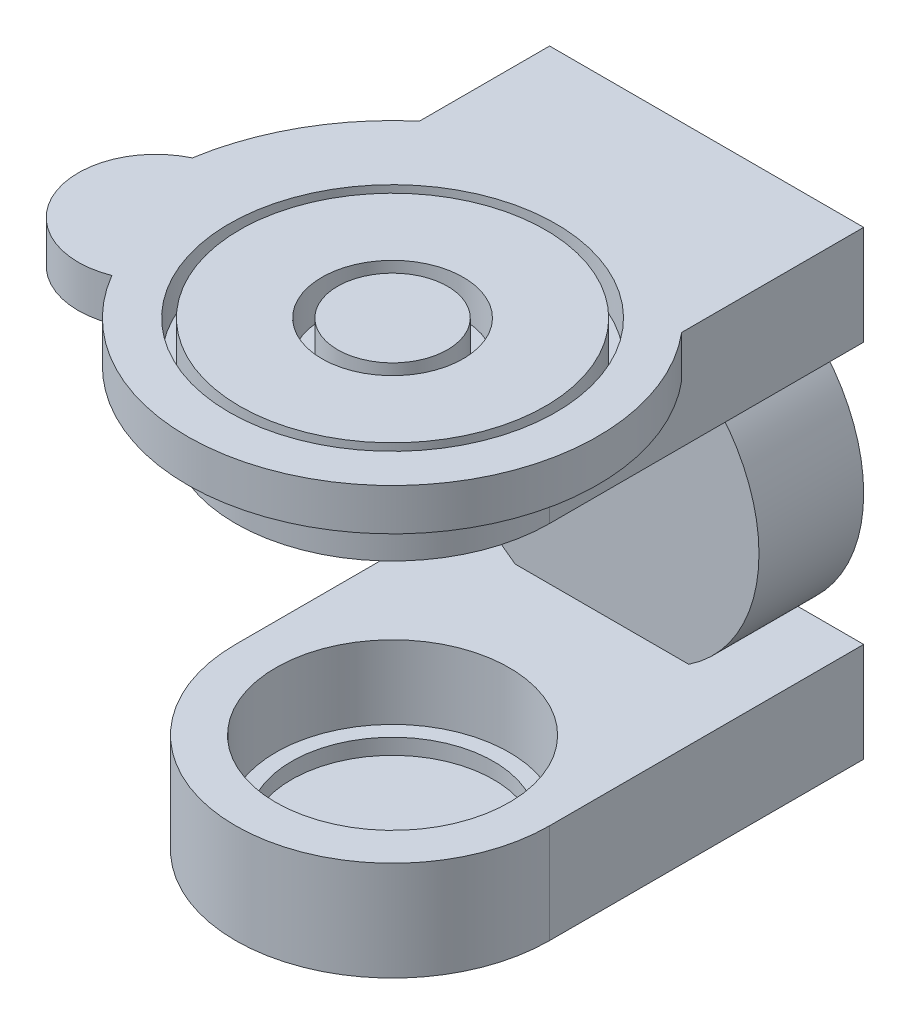
SolidWorks part; units mm, degrees
ref_plane "Спереди" through (0, 0, 0) normal (0, 0, 1) x (1, 0, 0)
ref_plane "Сверху" through (0, 0, 0) normal (0, 1, 0) x (1, 0, 0)
ref_plane "Справа" through (0, 0, 0) normal (1, 0, 0) x (0, 0, -1)
sketch "Эскиз основы" plane through (0, 0, 0) normal (0, 0, 1) x (1, 0, 0)
  circle A0 centre (0, 0) radius 15
  dimension "D1" = 30
extrude "Под крепеж" add sketch "Эскиз основы" along normal blind 10
ref_plane "Плоскость1" through (0, -15, 0) normal (0, -1, 0) x (-1, 0, 0)
sketch "Эскиз2" plane through (0, -15, 0) normal (0, -1, 0) x (-1, 0, 0)
  line L0 (-15, -10) -> (-15, -30)
  line L1 (15, 0) -> (-15, 0)
  line L2 (15, 0) -> (15, -10)
  line L3 (15, -10) -> (-15, -10)
  line L4 (-15, 0) -> (-15, -10)
  line L6 (15, -30) -> (15, -10)
  arc A0 (15, -30) -> (-15, -30) centre (0, -30) cw
  point P6 (0, -45)
  point P9 (0, -10)
  dimension "D1" = 15
  dimension "D2" = 20
extrude "Для крепления клешней" add sketch "Эскиз2" against normal blind 2.5 and the other way blind 7 contours L1 L4 L3 L2 | L6 L3 L0 region at (0, -15, 26.0668) region at (0, -15, 5)
sketch "Эскиз под подшипник" plane through (0, -12.5, 0) normal (0, 1, 0) x (1, 0, 0)
  line L0 (0, 0) -> (0, -30) construction
  line L1 (0, -30) -> (15, -30) construction
  circle A0 centre (0, -30) radius 11.15
  circle A1 centre (0, -30) radius 9.65
  dimension "D1" = 22.3
  dimension "D2" = 19.3
extrude "Выемка под подшипник" cut sketch "Эскиз под подшипник" against normal blind 8.5 contours A1 | A1 region at (0, -12.5, 30)
extrude "Вырез под подшипник" cut sketch "Эскиз4<3>" against normal blind 7 contours A0 A1 region at (-10.8346, -12.5, 30)
sketch "Эскиз4<3>" plane through (0, -12.5, 0) normal (0, 1, 0) x (1, 0, 0) same geometry as "Эскиз под подшипник"
mirror "Зеркальное отражение2" about plane through (0, 0, 0) normal (0, 1, 0) of "Вырез под подшипник", "Выемка под подшипник", "Для крепления клешней"
sketch "Эскиз под резистор" plane through (0, 22, 0) normal (0, 1, 0) x (1, 0, 0)
  line L0 (-15, -30) -> (15, -30) construction
  circle A0 centre (0, -30) radius 3.6
  dimension "D1" = 7.2
extrude "Вырез(отверстие) под резистор" cut sketch "Эскиз под резистор" against normal up to next
sketch "Эскиз4" plane through (0, 22, 0) normal (0, 1, 0) x (1, 0, 0)
  line L0 (0, -8.9) -> (0, -47.6) construction
  line L1 (15.6, -30) -> (-15.6, -30) construction
  line L2 (14.9, -17.2662) -> (14.9, -11.5209)
  line L6 (-15, 0) -> (-15, -30)
  line L7 (15, -30) -> (15, 0)
  line L8 (-15, 0) -> (15, 0)
  line L12 (0, -30) -> (-20.8576, -33.1889) construction
  line L13 (-18.6886, -30.8341) -> (-21.1599, -31.2119)
  line L14 (-16.4093, -32.5088) -> (-22.8347, -33.4912)
  line L15 (-18.0841, -34.7881) -> (-20.5554, -35.1659)
  line L16 (12.9, -18.0271) -> (12.9, -11.5209)
  circle A4 centre (0, -30) radius 14.6
  circle A5 centre (0, -30) radius 6.75
  circle A8 centre (0, -30) radius 5.25
  circle A11 centre (0, -30) radius 15
  arc A13 (-16.9219, -39.8898) -> (-22.8049, -26.3195) centre (-19.622, -33) cw
  arc A16 (-22.8049, -26.3195) -> (1.9933, -6.9862) centre (0, -30) cw
  arc A17 (1.9933, -6.9862) -> (14.9, -11.5209) centre (7.65, -11.5209) cw
  circle A18 centre (0, -30) radius 15.6
  arc A19 (12.9, -18.0271) -> (-16.1053, -37.0979) centre (0, -30) cw
  arc A20 (-20.5554, -35.1659) -> (-21.1599, -31.2119) centre (-20.8576, -33.1889) cw
  arc A21 (-18.6886, -30.8341) -> (-18.0841, -34.7881) centre (-18.3863, -32.8111) cw
  arc A22 (-16.1053, -37.0979) -> (-20.9823, -27.7741) centre (-19.622, -33) cw
  arc A23 (-20.9823, -27.7741) -> (2.9851, -9.1122) centre (0, -30) cw
  arc A24 (2.9851, -9.1122) -> (12.9, -11.5209) centre (7.65, -11.5209) cw
  circle A25 centre (7.65, -11.5209) radius 3.25
  arc A26 (14.9, -17.2662) -> (-16.9219, -39.8898) centre (0, -30) cw
  circle A27 centre (0, -30) radius 11.15 construction
  point P0 (0, -30)
  line M7 (-15, 0) -> (-15, -30)
  arc M8 (-15, -30) -> (15, -30) centre (0, -30) ccw
  line M9 (15, -30) -> (15, 0)
  dimension "D1" = 13.5
  dimension "D3" = 2
extrude "Бобышка-Вытянуть3" add sketch "Эскиз4" against normal blind 4 contours A26 A19 A22 A23 L6 A16 A13 M9 | A23 A22 A19 L7 A18 L13 A21 L15 A20 M7 | A21 L14 A20 L15 | A21 L13 A20 L14 | A18 region at (10.9502, 22, 45.5317) region at (7.9222, 22, 45.1139) region at (-19.7604, 22, 32.0947) region at (-19.4836, 22, 33.9053)
extrude "Вырез-Вытянуть1" cut sketch "Эскиз4<5>" against normal blind 3.5 contours A11 A4 M8 | A18 M7 M9 M8 | A18 A11 M9 M7 | A5 A8 region at (15.0829, 22, 27.888) region at (14.9662, 22, 27.8576) region at (0, 22, 44.9576) region at (-6.5591, 22, 30)
sketch "Эскиз4<5>" plane through (0, 22, 0) normal (0, 1, 0) x (1, 0, 0) same geometry as "Эскиз4"
